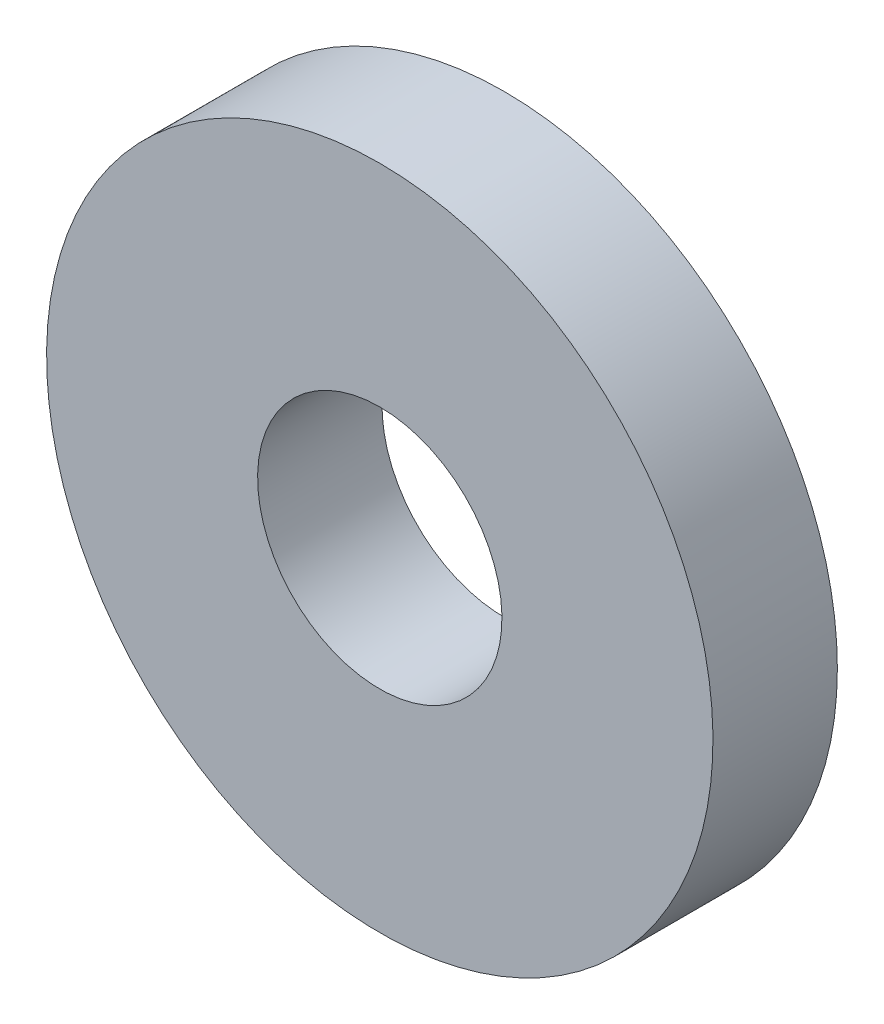
SolidWorks part; units mm, degrees
ref_plane "Front Plane" through (0, 0, 0) normal (0, 0, 1) x (1, 0, 0)
ref_plane "Top Plane" through (0, 0, 0) normal (0, 1, 0) x (1, 0, 0)
ref_plane "Right Plane" through (0, 0, 0) normal (1, 0, 0) x (0, 0, -1)
sketch "Sketch1" plane through (0, 0, 0) normal (0, 0, 1) x (1, 0, 0)
  circle A0 centre (0, 0) radius 7.5
  circle A1 centre (0, 0) radius 2.75
  circle A2 centre (0, 0) radius 7.5 construction
  circle A5 centre (12.7413, 38.3347) radius 2.75 construction
extrude "Boss-Extrude1" add sketch "Sketch1" along normal up to surface (2.8 mm away) contours A0 A1 region at (-7.2879, 0, 0)
